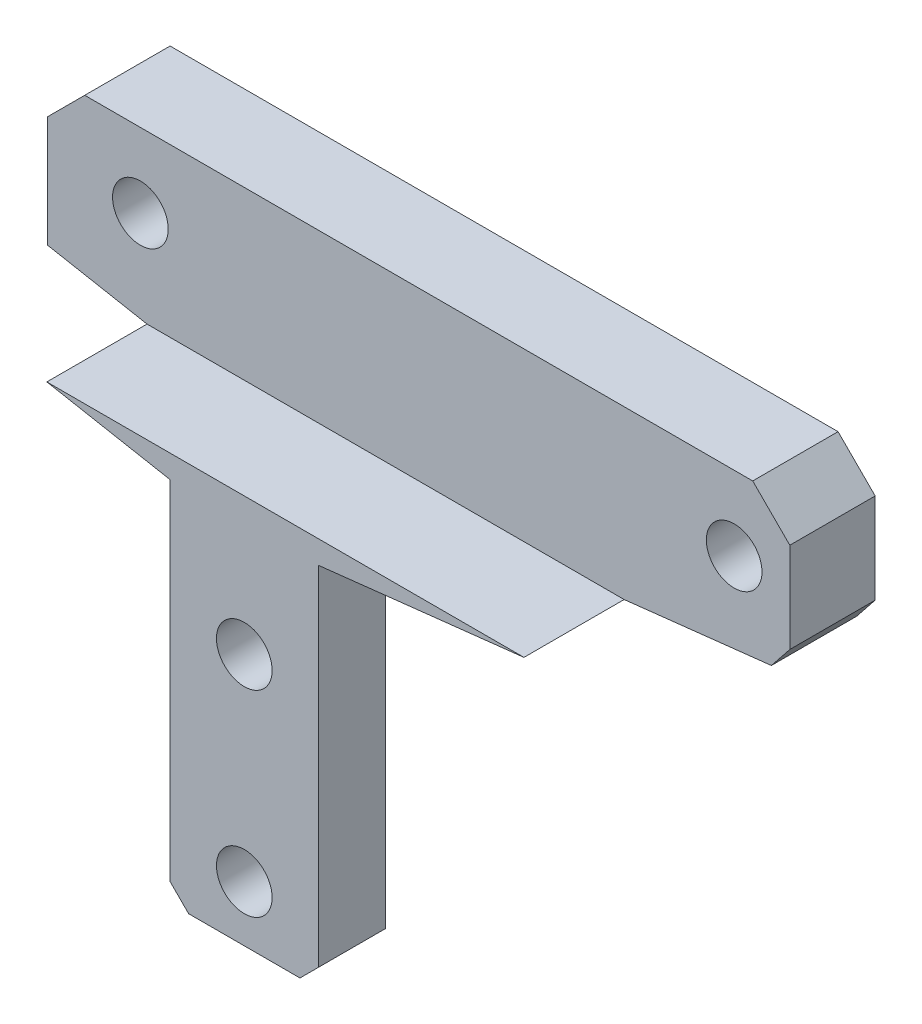
SolidWorks part; units mm, degrees
ref_plane "前视基准面" through (0, 0, 0) normal (0, 0, 1) x (1, 0, 0)
ref_plane "上视基准面" through (0, 0, 0) normal (0, 1, 0) x (1, 0, 0)
ref_plane "右视基准面" through (0, 0, 0) normal (1, 0, 0) x (0, 0, -1)
other "Configuration Table"
sketch "草图1" plane through (0, 0, 0) normal (0, 0, 1) x (1, 0, 0)
  line L1 (-10, 2) -> (10, 2)
  line L2 (-10, 2) -> (-10, -2)
  line L4 (10, 2) -> (10, -2)
  line L5 (-10, 2) -> (10, -2) construction
  line L6 (-10, -2) -> (10, 2) construction
  line L8 (-4, -3.12) -> (-4, -13)
  line L9 (-4, -13) -> (0, -13)
  line L10 (0, -3.12) -> (0, -13)
  line L11 (-10, -2) -> (-4, -3.12)
  line L12 (0, -3.12) -> (10, -2)
  circle A0 centre (-7.5, 0) radius 0.75
  circle A1 centre (8.5, 0) radius 0.75
  circle A2 centre (-2, -11.5) radius 0.75
  circle A3 centre (-2, -6.2) radius 0.75
  point P0 (0, 0)
  dimension "D5" = 9.88
  dimension "D7" = 1.12
  dimension "D13" = 1.5
  dimension "D1" = 20
  dimension "D2" = 4
  dimension "D3" = 4
  dimension "D4" = 1.12
  dimension "D6" = 2.5
  dimension "D8" = 1.5
  dimension "D9" = 10
  dimension "D10" = 2
  dimension "D11" = 2
  dimension "D14" = 2
  dimension "D15" = 2
  dimension "D16" = 1.5
  dimension "D17" = 5.3
extrude "凸台-拉伸2" add sketch "草图1" along normal blind 5.5
sketch "草图3" plane through (0, 0, 0) normal (0, 0, -1) x (-1, 0, 0)
  line L0 (0, -3.12) -> (4, -3.12)
  line L8 (-10, 2) -> (-10, -2)
  line L9 (-10, -2) -> (0, -3.12)
  line L10 (0, -3.12) -> (0, -13)
  line L11 (0, -13) -> (4, -13)
  line L12 (4, -13) -> (4, -3.12)
  line L14 (10, -2) -> (10, 2)
  line L15 (10, 2) -> (-10, 2)
  line L18 (0, -3.12) -> (0, -13)
  line L19 (0, -13) -> (4, -13)
  line L20 (4, -13) -> (4, -3.12)
  line L25 (4, -3.12) -> (10, -2)
  circle A0 centre (2, -11.5) radius 0.75 construction
  circle A1 centre (2, -6.2) radius 0.75 construction
  circle A2 centre (2, -11.5) radius 0.75
  circle A3 centre (2, -6.2) radius 0.75
  dimension "D2" = 0
  dimension "D1" = 0
extrude "切除-拉伸2" cut sketch "草图3" against normal blind 4.2
chamfer "倒角1" distance 1 angle 45 1 edges at (-2, -3.12, 4.2)
chamfer "倒角2" distance 1 angle 45 2 edges at (-10, 2, 2.75) (10, 2, 2.75)
chamfer "倒角3" distance 0.5 angle 45 2 edges at (-4, -13, 4.85) (0, -13, 4.85)
sketch "草图4" plane through (0, 0, 5.5) normal (0, 0, 1) x (1, 0, 0)
  line L6 (-10, -2.5) -> (10, -2.5)
  line L12 (-4, -3.12) -> (-4, -12.5)
  line L13 (-4, -12.5) -> (-3.5, -13)
  line L14 (-3.5, -13) -> (-0.5, -13)
  line L15 (-0.5, -13) -> (0, -12.5)
  line L16 (0, -12.5) -> (0, -3.12)
  line L17 (0, -3.12) -> (10, -2)
  line L18 (10, -2) -> (10, 1)
  line L19 (10, 1) -> (9, 2)
  line L20 (9, 2) -> (-9, 2)
  line L21 (-9, 2) -> (-10, 1)
  line L22 (-10, 1) -> (-10, -2)
  line L23 (-10, -2) -> (-4, -3.12)
  line L30 (10, -2.5) -> (10, 1)
  line L31 (10, 1) -> (9, 2)
  line L32 (9, 2) -> (-9, 2)
  line L33 (-9, 2) -> (-10, 1)
  line L34 (-10, 1) -> (-10, -2.5)
  circle A0 centre (8.5, 0) radius 0.75 construction
  circle A1 centre (-7.5, 0) radius 0.75 construction
  circle A2 centre (8.5, 0) radius 0.75
  circle A3 centre (-7.5, 0) radius 0.75
  dimension "D2" = 4.5
  dimension "D1" = 0
extrude "切除-拉伸3" cut sketch "草图4" against normal blind 2.2
chamfer "倒角4" distance 0.5 angle 45 1 edges at (10, -2, 1.65) first distance on face at (4.4388, -2.6229, 2.9714)
sketch "草图5" plane through (0, 0, 0) normal (0, 0, -1) x (-1, 0, 0)
  line L11 (-10, 1) -> (-10, -1.4334)
  line L12 (-10, -1.4334) -> (-9.5031, -2.0557)
  line L13 (-9.5031, -2.0557) -> (0, -3.12)
  line L15 (0, -3.12) -> (4, -3.12)
  line L17 (4, -3.12) -> (10, -2)
  line L18 (10, -2) -> (10, 1)
  line L19 (10, 1) -> (9, 2)
  line L20 (9, 2) -> (-9, 2)
  line L21 (-9, 2) -> (-10, 1)
  line L22 (-10, 1) -> (-10, -1.4334)
  line L23 (-10, -1.4334) -> (-9.5031, -2.0557)
  line L24 (-9.5031, -2.0557) -> (0, -3.12)
  line L26 (0, -3.12) -> (4, -3.12)
  line L28 (4, -3.12) -> (10, -2)
  line L29 (10, -2) -> (10, 1)
  line L30 (10, 1) -> (9, 2)
  line L31 (9, 2) -> (-9, 2)
  line L32 (-9, 2) -> (-10, 1)
  circle A0 centre (7.5, 0) radius 0.75 construction
  circle A1 centre (-8.5, 0) radius 0.75 construction
  circle A2 centre (7.5, 0) radius 0.75
  circle A3 centre (-8.5, 0) radius 0.75
  dimension "D1" = 0
extrude "切除-拉伸4" cut sketch "草图5" against normal blind 1
sketch "草图6" plane through (0, 0, 5.5) normal (0, 0, 1) x (1, 0, 0)
  line L8 (0, -3.12) -> (5.5357, -2.5)
  line L9 (5.5357, -2.5) -> (-7.3214, -2.5)
  line L10 (-7.3214, -2.5) -> (-4, -3.12)
  line L11 (-4, -3.12) -> (-4, -12.5)
  line L12 (-4, -12.5) -> (-3.5, -13)
  line L13 (-3.5, -13) -> (-0.5, -13)
  line L14 (-0.5, -13) -> (0, -12.5)
  line L15 (0, -12.5) -> (0, -3.12)
  line L16 (0, -3.12) -> (5.5357, -2.5)
  line L17 (5.5357, -2.5) -> (-7.3214, -2.5)
  line L18 (-7.3214, -2.5) -> (-4, -3.12)
  line L19 (-4, -3.12) -> (-4, -12.5)
  line L20 (-4, -12.5) -> (-3.5, -13)
  line L21 (-3.5, -13) -> (-0.5, -13)
  line L22 (-0.5, -13) -> (0, -12.5)
  line L23 (0, -12.5) -> (0, -3.12)
  circle A0 centre (-2, -11.5) radius 0.75 construction
  circle A1 centre (-2, -6.2) radius 0.75 construction
  circle A2 centre (-2, -11.5) radius 0.75
  circle A3 centre (-2, -6.2) radius 0.75
  dimension "D1" = 0
extrude "凸台-拉伸3" add sketch "草图6" along normal blind 0.5
